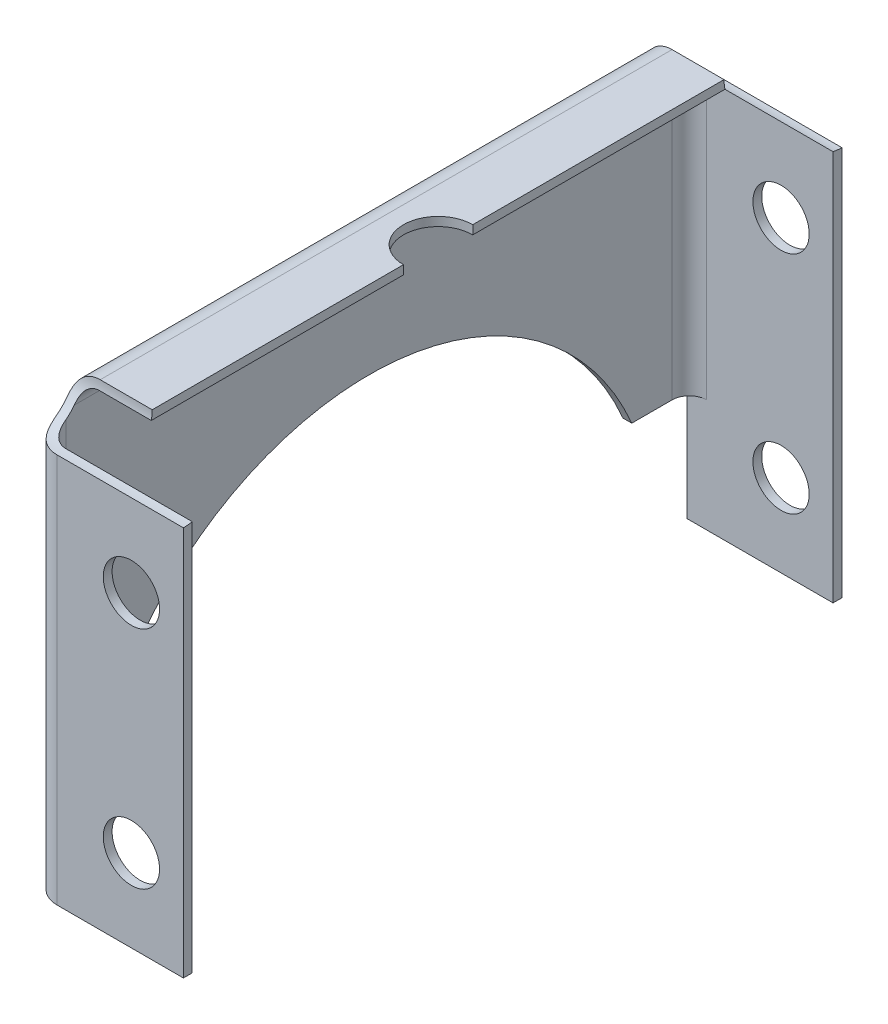
SolidWorks part; units mm, degrees
ref_plane "Front Plane" through (0, 0, 0) normal (0, 0, 1) x (1, 0, 0)
ref_plane "Top Plane" through (0, 0, 0) normal (0, 1, 0) x (1, 0, 0)
ref_plane "Right Plane" through (0, 0, 0) normal (1, 0, 0) x (0, 0, -1)
sketch "Sketch1" plane through (0, 0, 0) normal (1, 0, 0) x (0, 0, -1)
  line L0 (48.26, 63.5) -> (48.26, 31.75) construction
  line L1 (1.2954, 16.51) -> (1.2954, 0)
  line L2 (0, 0) -> (0, 63.5)
  line L3 (0, 63.5) -> (96.52, 63.5)
  line L4 (96.52, 0) -> (96.52, 63.5)
  line L5 (0, 31.75) -> (96.52, 31.75) construction
  line L6 (86.781, 16.51) -> (95.2246, 16.51)
  line L7 (1.2954, 0) -> (0, 0)
  line L8 (95.2246, 16.51) -> (95.2246, 0)
  line L9 (95.2246, 0) -> (96.52, 0)
  line L10 (9.739, 16.51) -> (1.2954, 16.51)
  circle A0 centre (0, 63.5) radius 6.35
  circle A1 centre (96.52, 63.5) radius 6.35
  arc A2 (86.781, 16.51) -> (9.739, 16.51) centre (48.26, 0) ccw
  dimension "D3" = 12.7
  dimension "D4" = 83.82
  dimension "D7" = 12.7
  dimension "D1" = 63.5
  dimension "D2" = 96.52
  dimension "D5" = 1.2954
  dimension "D6" = 16.51
  dimension "D8" = 9.739
extrude "Boss-Extrude3" add sketch "Sketch1" along normal blind 22.352 contours A2 L6 L8 L9 L4 A1 L3 A0 L2 L7 L1 L10 region at (0, 45.0639, -48.26)
shell "Shell3" thickness 1.2954 removed face at (11.176, 16.51, -91.0028) removed face at (11.176, 16.51, -5.5172) removed face at (11.176, 29.21, -48.26) removed face at (22.352, 27.5091, -48.26) removed face at (11.176, 59.6674, -3.8326) removed face at (11.176, 59.6674, -92.6874)
fillet "Fillet1" radius 3.81 3 edges at (0, 28.575, -96.52) (0, 63.5, -48.26) (0, 28.575, 0)
sketch "Sketch2" plane through (0, 63.5, 0) normal (0, 1, 0) x (1, 0, 0)
  line L0 (22.352, 95.2246) -> (11.43, 95.2246)
  line L2 (11.43, 95.2246) -> (11.43, 1.2954)
  line L4 (11.43, 1.2954) -> (22.352, 1.2954)
  line L5 (22.352, 1.2954) -> (22.352, 95.2246)
  line L6 (0, 5.08) -> (0, 91.44) construction
  line L7 (22.352, 95.2246) -> (1.2954, 95.2246) construction
  line L8 (22.352, 1.2954) -> (1.2954, 1.2954) construction
  circle A0 centre (11.43, 48.26) radius 5.08
  line M1 (22.352, 90.17) -> (3.81, 90.17)
  line M3 (3.81, 6.35) -> (22.352, 6.35)
  line M4 (22.352, 6.35) -> (22.352, 90.17)
  dimension "D2" = 10.16
  dimension "D1" = 11.43
  dimension "D3" = 10.922
extrude "Cut-Extrude1" cut sketch "Sketch2" against normal through all contours A0 L2 M3 M4 M1 | L2 A0 | L2 A0 | L4 L5 L2 M3 | L5 L0 L2 M1 region at (16.891, 63.5, -92.6973) region at (17.0441, 63.5, -48.26) region at (16.891, 63.5, -3.8227) region at (13.586, 63.5, -48.26) region at (9.274, 63.5, -48.26)
sketch "Sketch3" plane through (0, 0, 0) normal (0, 0, 1) x (1, 0, 0)
  line L0 (14.732, 45.085) -> (14.732, 12.065) construction
  line L3 (22.352, 57.2835) -> (22.352, 0) construction
  line L4 (22.352, 28.575) -> (3.81, 28.575) construction
  line L5 (22.352, 0) -> (22.352, 57.15) construction
  line L6 (3.81, 57.15) -> (3.81, 0) construction
  circle A0 centre (14.732, 45.085) radius 4.1275
  circle A1 centre (14.732, 12.065) radius 4.1275
  point P0 (14.732, 28.575)
  dimension "D3" = 8.255
  dimension "D1" = 7.62
  dimension "D2" = 33.02
extrude "Cut-Extrude2" cut sketch "Sketch3" against normal through all
fillet "Fillet2" radius 2.54 3 edges at (1.2954, 36.8968, -95.2246) (1.2954, 36.8968, -1.2954) (1.2954, 62.2046, -48.26)
